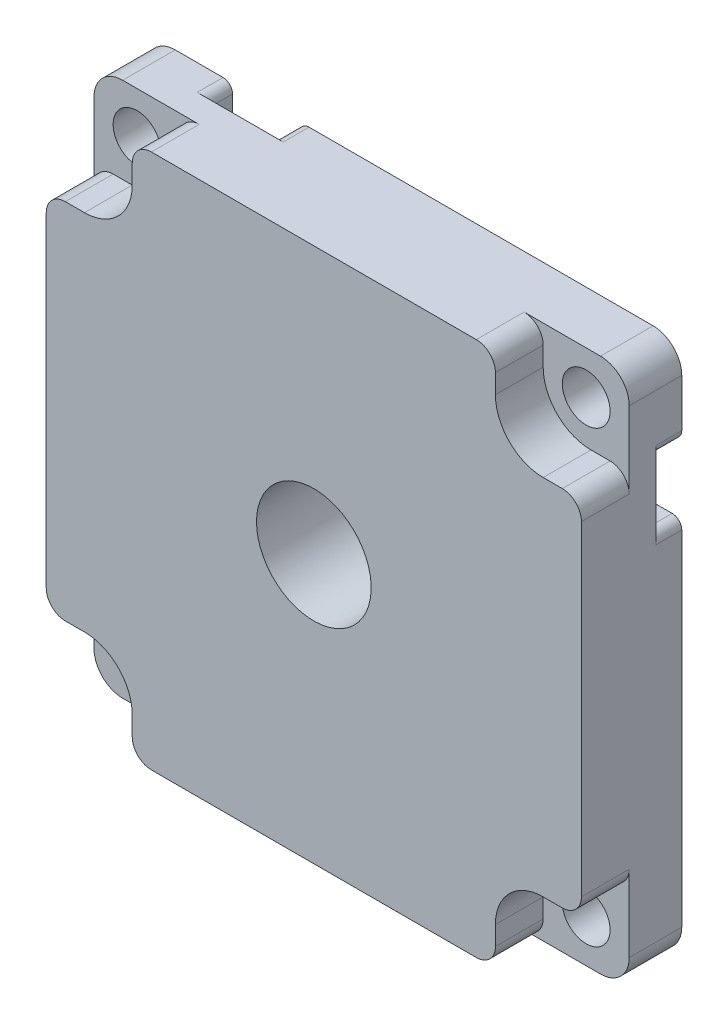
SolidWorks part; units mm, degrees
material "1060 Alloy"
ref_plane "Front Plane" through (0, 0, 0) normal (0, 0, 1) x (1, 0, 0)
ref_plane "Top Plane" through (0, 0, 0) normal (0, 1, 0) x (1, 0, 0)
ref_plane "Right Plane" through (0, 0, 0) normal (1, 0, 0) x (0, 0, -1)
sketch "Sketch1" plane through (0, 0, 0) normal (0, 0, 1) x (1, 0, 0)
  line L1 (28, -28) -> (-28, -28)
  line L2 (28, -28) -> (28, 28)
  line L3 (28, 28) -> (-28, 28)
  line L4 (-28, -28) -> (-28, 28)
  line L5 (28, -28) -> (-28, 28) construction
  line L6 (28, 28) -> (-28, -28) construction
  point P0 (0, 0)
  dimension "D1" = 56
  dimension "D2" = 56
extrude "Boss-Extrude1" add sketch "Sketch1" along normal blind 10.5
sketch "Sketch4" plane through (0, 0, 0) normal (0, 0, -1) x (-1, 0, 0)
  circle A0 centre (0, 0) radius 19
  dimension "D1" = 38
extrude "Boss-Extrude4" add sketch "Sketch4" along normal blind 1.5
fillet "Fillet1" radius 0.5 1 edges at (19, 0, 0)
fillet "Fillet2" radius 3 4 edges at (28, -28, 5.25) (-28, -28, 5.25) (-28, 28, 5.25) (28, 28, 5.25)
ref_axis "Axis1" through (0, 0, 11.1) along (0, 0, -1)
sketch "Sketch5" plane through (0, 0, -1.5) normal (0, 0, -1) x (-1, 0, 0)
  circle A0 centre (0, 0) radius 6
  dimension "D1" = 12
extrude "Cut-Extrude1" cut sketch "Sketch5" against normal through all
hole_wizard "Ø5.0mm Dowel Hole1" positions "Sketch6" profile "Sketch7" hole size "Ø5.0" standard "ISO"
sketch "Sketch6" plane through (0, 0, 0) normal (0, 0, -1) x (-1, 0, 0)
  line L0 (-28, -25) -> (-28, 25) construction
  line L1 (-25, 28) -> (25, 28) construction
  point P0 (-23.5, 23.5)
  dimension "D1" = 4.5
  dimension "D2" = 4.5
sketch "Sketch7" plane through (23.5, 23.5, 0) normal (1, 0, 0) x (0, 1, 0)
  line L0 (0, 0) -> (0, 18.5022)
  line L1 (0, 18.5022) -> (2.5, 17)
  line L2 (2.5, 17) -> (2.5, 0)
  line L5 (2.5, 0) -> (0, 0)
  line L10 (0, 18.5022) -> (-2.5, 17) construction
  line L11 (0, -6.35) -> (0, 107.95) construction
  dimension "Hole Dia." = 5
  dimension "Hole Depth" = 17
  dimension "Drill Angle" = 118
sketch "Sketch8" plane through (0, 0, 0) normal (0, 0, -1) x (-1, 0, 0)
  line L0 (12, 28) -> (12, 22)
  line L1 (-25, 28) -> (25, 28) construction
  line L2 (12, 22) -> (19, 22)
  line L3 (19, 22) -> (19, 28)
  line L4 (19, 28) -> (12, 28)
  line L5 (-28, -25) -> (-28, 25) construction
  dimension "D1" = 40
  dimension "D2" = 7
  dimension "D3" = 6
extrude "Cut-Extrude2" cut sketch "Sketch8" against normal blind 2.7
pattern_circular "CirPattern7" count 4 over 360 about axis through (0, 0, 11.1) along (0, 0, -1) of "Cut-Extrude2"
fillet "Fillet5" radius 1 8 edges at (28, 12, 1.35) (28, 19, 1.35) (12, -28, 1.35) (19, -28, 1.35) (-28, -19, 1.35) (-28, -12, 1.35) (-19, 28, 1.35) (-12, 28, 1.35)
fillet "Fillet6" radius 3.5 8 edges at (-12, 22, 1.35) (-19, 22, 1.35) (22, 12, 1.35) (22, 19, 1.35) (12, -22, 1.35) (19, -22, 1.35) (-22, -19, 1.35) (-22, -12, 1.35)
sketch "Sketch10" plane through (0, 0, 10.5) normal (0, 0, 1) x (1, 0, 0)
  line L0 (-28, 19) -> (-19, 19)
  line L1 (-28, 25) -> (-28, -25) construction
  line L2 (-19, 19) -> (-19, 28)
  line L3 (25, 28) -> (-25, 28) construction
  line L4 (-19, 28) -> (-28, 28)
  line L5 (-28, 28) -> (-28, 19)
  dimension "D1" = 9
  dimension "D2" = 9
extrude "Cut-Extrude4" cut sketch "Sketch10" against normal blind 5
pattern_circular "CirPattern11" count 4 over 360 about axis through (0, 0, 11.1) along (0, 0, -1) of "Cut-Extrude4"
fillet "Fillet8" radius 2 8 edges at (-19, 28, 8) (-28, 19, 8) (-19, -28, 8) (-28, -19, 8) (28, -19, 8) (19, -28, 8) (28, 19, 8) (19, 28, 8)
fillet "Fillet9" radius 5 4 edges at (-19, 19, 8) (-19, -19, 8) (19, -19, 8) (19, 19, 8)
pattern_circular "CirPattern12" count 4 over 360 about axis through (0, 0, 11.1) along (0, 0, -1) of "Ø5.0mm Dowel Hole1"
